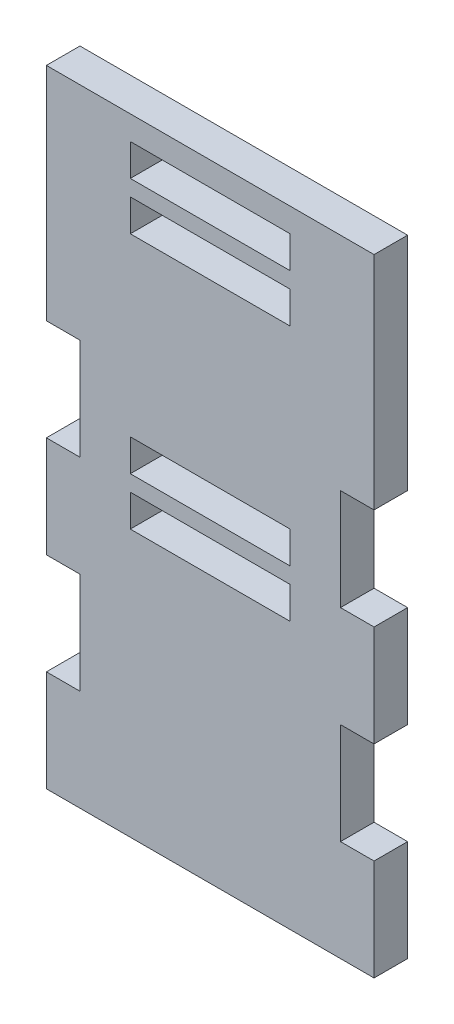
SolidWorks part; units mm, degrees
ref_plane "Front Plane" through (0, 0, 0) normal (0, 0, 1) x (1, 0, 0)
ref_plane "Top Plane" through (0, 0, 0) normal (0, 1, 0) x (1, 0, 0)
ref_plane "Right Plane" through (0, 0, 0) normal (1, 0, 0) x (0, 0, -1)
sketch "Sketch1" plane through (0, 0, 0) normal (0, 0, 1) x (1, 0, 0)
  line L1 (-38.9473, 40.8312) -> (13.1227, 40.8312)
  line L2 (-38.9473, 40.8312) -> (-38.9473, -39.6868)
  line L3 (-38.9473, -39.6868) -> (13.1227, -39.6868)
  line L4 (13.1227, 40.8312) -> (13.1227, -39.6868)
  dimension "D1" = 80.518
  dimension "D2" = 52.07
extrude "Boss-Extrude1" add sketch "Sketch1" along normal blind 5.334
sketch "Sketch2" plane through (0, 0, 5.334) normal (0, 0, 1) x (1, 0, 0)
  line L0 (-38.9473, 40.8312) -> (-38.9473, -39.6868) construction
  line L1 (-38.9473, 24.7276) -> (-33.6133, 24.7276)
  line L2 (-38.9473, 24.7276) -> (-38.9473, 8.624)
  line L3 (-38.9473, 8.624) -> (-33.6133, 8.624)
  line L4 (-33.6133, 24.7276) -> (-33.6133, 8.624)
  line L5 (-33.6133, 24.7276) -> (-33.6133, 40.8312) construction
  line L6 (-38.9473, -7.4796) -> (-33.6133, -7.4796)
  line L7 (-38.9473, -7.4796) -> (-38.9473, -23.5832)
  line L8 (-38.9473, -23.5832) -> (-33.6133, -23.5832)
  line L9 (-33.6133, -7.4796) -> (-33.6133, -23.5832)
  line L10 (13.1227, 40.8312) -> (-38.9473, 40.8312) construction
  line L11 (-33.6133, 8.624) -> (-33.6133, -7.4796) construction
  line L12 (-33.6133, -7.4796) -> (-33.9376, -7.3715) construction
  line L13 (-33.6133, -23.5832) -> (-33.6133, -39.6868) construction
  line L14 (-38.9473, -39.6868) -> (13.1227, -39.6868) construction
  line L15 (-12.9123, 40.8312) -> (-12.9123, -39.6868) construction
  line L16 (7.7887, -23.5832) -> (7.7887, -39.6868) construction
  line L17 (7.7887, -7.4796) -> (8.113, -7.3715) construction
  line L18 (7.7887, 8.624) -> (7.7887, -7.4796) construction
  line L19 (7.7887, 24.7276) -> (7.7887, 40.8312) construction
  line L20 (7.7887, -7.4796) -> (7.7887, -23.5832)
  line L21 (13.1227, -23.5832) -> (7.7887, -23.5832)
  line L22 (13.1227, -7.4796) -> (13.1227, -23.5832)
  line L23 (13.1227, -7.4796) -> (7.7887, -7.4796)
  line L24 (7.7887, 24.7276) -> (7.7887, 8.624)
  line L25 (13.1227, 8.624) -> (7.7887, 8.624)
  line L26 (13.1227, 24.7276) -> (13.1227, 8.624)
  line L27 (13.1227, 24.7276) -> (7.7887, 24.7276)
  dimension "D1" = 5.334
extrude "Cut-Extrude1" cut sketch "Sketch2" against normal through all
sketch "Sketch4" plane through (0, 0, 5.334) normal (0, 0, 1) x (1, 0, 0)
  line L0 (13.1227, 24.7276) -> (13.1227, 40.8312) construction
  line L1 (-38.9473, 24.7276) -> (13.1227, 24.7276)
  line L2 (-38.9473, 24.7276) -> (-38.9473, 59.8812)
  line L3 (-38.9473, 59.8812) -> (13.1227, 59.8812)
  line L4 (13.1227, 24.7276) -> (13.1227, 59.8812)
  line L5 (13.1227, 40.8312) -> (-38.9473, 40.8312) construction
  dimension "D1" = 0
  dimension "D2" = 19.05
extrude "Boss-Extrude2" add sketch "Sketch4" against normal blind 5.334
sketch "Sketch5" plane through (0, 0, 5.334) normal (0, 0, 1) x (1, 0, 0)
  line L0 (-12.9123, 59.8812) -> (-12.9123, -39.6868) construction
  line L1 (13.1227, 59.8812) -> (-38.9473, 59.8812) construction
  line L2 (-38.9473, -39.6868) -> (13.1227, -39.6868) construction
  line L3 (-25.6123, 15.4312) -> (-0.2123, 15.4312)
  line L4 (-25.6123, 56.0712) -> (-0.2123, 56.0712)
  line L5 (-25.6123, 56.0712) -> (-25.6123, 50.9912)
  line L6 (-25.6123, 50.9912) -> (-0.2123, 50.9912)
  line L7 (-0.2123, 56.0712) -> (-0.2123, 50.9912)
  line L8 (-25.6123, 10.3512) -> (-0.2123, 10.3512)
  line L9 (-25.6123, 15.4312) -> (-25.6123, 10.3512)
  line L10 (-0.2123, 15.4312) -> (-0.2123, 10.3512)
  line L11 (-25.6123, 48.4512) -> (-0.2123, 48.4512)
  line L12 (-25.6123, 43.3712) -> (-0.2123, 43.3712)
  line L13 (-25.6123, 48.4512) -> (-25.6123, 43.3712)
  line L14 (-0.2123, 48.4512) -> (-0.2123, 43.3712)
  line L19 (-25.6123, 7.8112) -> (-0.2123, 7.8112)
  line L20 (-25.6123, 2.7312) -> (-0.2123, 2.7312)
  line L21 (-25.6123, 7.8112) -> (-25.6123, 2.7312)
  line L22 (-0.2123, 7.8112) -> (-0.2123, 2.7312)
  dimension "D1" = 5.08
  dimension "D2" = 12.7
  dimension "D3" = 25.4
  dimension "D4" = 3.81
  dimension "D5" = 2
  dimension "D6" = 2
  dimension "D8" = 2
extrude "Cut-Extrude5" cut sketch "Sketch5" against normal through all
equation "\"MDF\"= .21in"
equation "\"Foamcore\"= .13in"
equation "\"Gmaterial\"= \"MDF\""
equation "\"D2@Sketch1\"=2*\"MDF\"+1.63"
equation "\"D1@Boss-Extrude1\"=\"MDF\""
equation "\"D1@Sketch2\"=\"MDF\""
